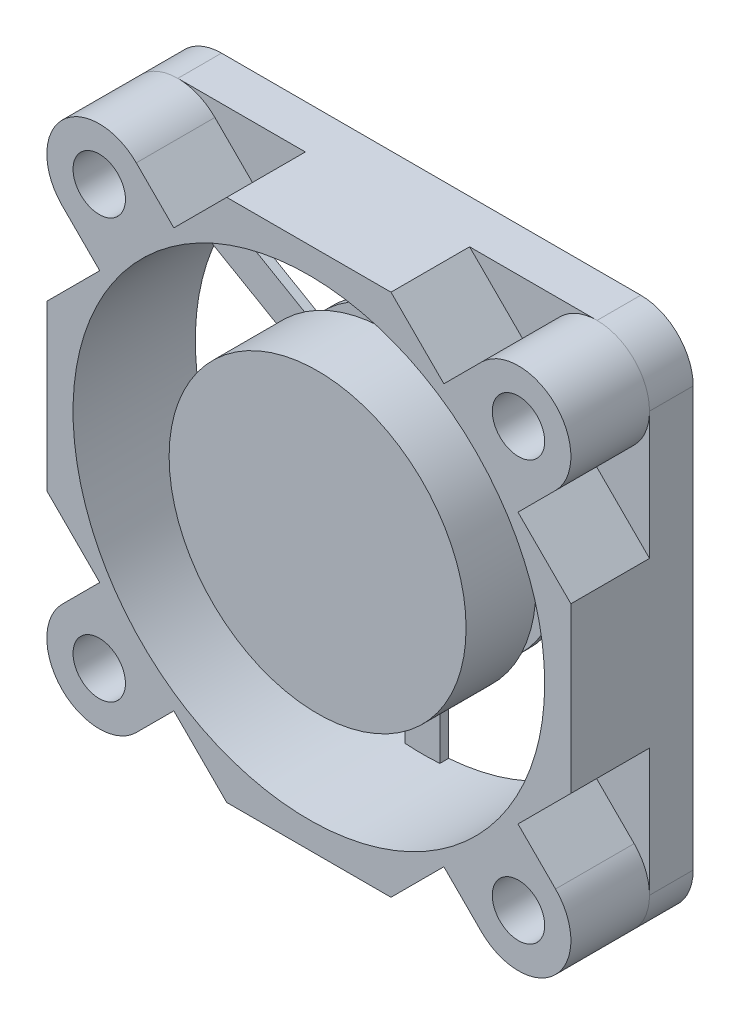
SolidWorks part; units mm, degrees
ref_plane "Спереди" through (0, 0, 0) normal (0, 0, 1) x (1, 0, 0)
ref_plane "Сверху" through (0, 0, 0) normal (0, 1, 0) x (1, 0, 0)
ref_plane "Справа" through (0, 0, 0) normal (1, 0, 0) x (0, 0, -1)
sketch "Эскиз1" plane through (0, 0, 0) normal (0, 0, 1) x (1, 0, 0)
  line L0 (-1, -7.9373) -> (-1, -13.4629)
  line L1 (15, -15) -> (-15, -15)
  line L2 (15, -15) -> (15, 15)
  line L3 (15, 15) -> (-15, 15)
  line L4 (-15, -15) -> (-15, 15)
  line L5 (15, -15) -> (-15, 15) construction
  line L6 (15, 15) -> (-15, -15) construction
  line L7 (0, 0) -> (0, -15) construction
  line L8 (1, -7.9373) -> (1, -13.4629)
  line L9 (-6.3739, 4.8347) -> (-11.1592, 7.5975)
  line L10 (-7.3739, 3.1026) -> (-12.1592, 5.8654)
  line L11 (7.3739, 3.1026) -> (12.1592, 5.8654)
  line L12 (6.3739, 4.8347) -> (11.1592, 7.5975)
  arc A0 (-12.1592, 5.8654) -> (-1, -13.4629) centre (0, 0) ccw
  arc A1 (-7.3739, 3.1026) -> (-1, -7.9373) centre (0, 0) ccw
  arc A2 (1, -7.9373) -> (7.3739, 3.1026) centre (0, 0) ccw
  arc A3 (1, -13.4629) -> (12.1592, 5.8654) centre (0, 0) ccw
  arc A4 (6.3739, 4.8347) -> (-6.3739, 4.8347) centre (0, 0) ccw
  arc A5 (11.1592, 7.5975) -> (-11.1592, 7.5975) centre (0, 0) ccw
  circle A6 centre (-12, 12) radius 1.5
  circle A7 centre (12, 12) radius 1.5
  circle A8 centre (12, -12) radius 1.5
  circle A9 centre (-12, -12) radius 1.5
  point P0 (0, 0)
  point P24 (0, 0)
  dimension "D3" = 27
  dimension "D4" = 16
  dimension "D7" = 3
  dimension "D8" = 12
  dimension "D1" = 30
  dimension "D2" = 30
  dimension "D5" = 1
  dimension "D6" = 3
  dimension "D9" = 2
  dimension "D10" = 2
extrude "Бобышка-Вытянуть1" add sketch "Эскиз1" along normal blind 2.5
sketch "Эскиз2" plane through (0, 0, 2.5) normal (0, 0, 1) x (1, 0, 0)
  line L0 (-9.8787, 14.1213) -> (-7.7291, 11.9718)
  line L1 (0, 15) -> (0, -15) construction
  line L2 (15, 15) -> (-15, 15) construction
  line L3 (-15, -15) -> (15, -15) construction
  line L4 (-7.7291, 15) -> (-7.7291, 11.9718) construction
  line L5 (14.1213, 9.8787) -> (11.9718, 7.7291)
  line L6 (-7.7291, 11.9718) -> (-4.7009, 15)
  line L7 (-15, 15) -> (-9.5459, 9.5459) construction
  line L8 (9.8787, 14.1213) -> (7.7291, 11.9718)
  line L9 (-14.1213, 9.8787) -> (-11.9718, 7.7291)
  line L10 (-11.9718, 7.7291) -> (-15, 4.7009)
  line L11 (9.8787, -14.1213) -> (7.7291, -11.9718)
  line L12 (7.7291, 11.9718) -> (4.7009, 15)
  line L13 (14.1213, -9.8787) -> (11.9718, -7.7291)
  line L14 (-14.1213, -9.8787) -> (-11.9718, -7.7291)
  line L15 (-9.8787, -14.1213) -> (-7.7291, -11.9718)
  line L16 (11.9718, 7.7291) -> (15, 4.7009)
  line L18 (11.9718, -7.7291) -> (15, -4.7009)
  line L22 (7.7291, -11.9718) -> (4.7009, -15)
  line L24 (-7.7291, -11.9718) -> (-4.7009, -15)
  line L28 (-11.9718, -7.7291) -> (-15, -4.7009)
  line L29 (4.7009, 15) -> (-4.7009, 15)
  line L30 (15, 4.7009) -> (15, -4.7009)
  line L31 (4.7009, -15) -> (-4.7009, -15)
  line L32 (-15, -4.7009) -> (-15, 4.7009)
  line L34 (10.7574, 15) -> (7.7291, 11.9718) [skipped]
  line L35 (15, 10.7574) -> (11.9718, 7.7291) [skipped]
  line L36 (-10.7574, -15) -> (-7.7291, -11.9718) [skipped]
  line L37 (-15, -10.7574) -> (-11.9718, -7.7291) [skipped]
  line L38 (15, -10.7574) -> (11.9718, -7.7291) [skipped]
  line L39 (10.7574, -15) -> (7.7291, -11.9718) [skipped]
  circle A0 centre (-12, 12) radius 1.5
  circle A1 centre (-12, 12) radius 1.5 construction
  circle A2 centre (12, 12) radius 1.5
  circle A3 centre (12, -12) radius 1.5
  circle A4 centre (-12, -12) radius 1.5
  circle A5 centre (0, 0) radius 13.5
  arc A6 (11.1592, 7.5975) -> (-11.1592, 7.5975) centre (0, 0) ccw construction
  circle A7 centre (0, 0) radius 14.25 construction
  arc A8 (14.1213, 9.8787) -> (9.8787, 14.1213) centre (12, 12) ccw
  arc A9 (-9.8787, 14.1213) -> (-14.1213, 9.8787) centre (-12, 12) ccw
  arc A10 (9.8787, -14.1213) -> (14.1213, -9.8787) centre (12, -12) ccw
  arc A11 (-14.1213, -9.8787) -> (-9.8787, -14.1213) centre (-12, -12) ccw
  point P58 (0, 0)
  point P77 (0, 0)
  dimension "D1" = 2
  dimension "D3" = 45
  dimension "D5" = 28.5
  dimension "D8" = 4
  dimension "D4" = 3
  dimension "D6" = 90
  dimension "D7" = 4
  dimension "D2" = 2
extrude "Бобышка-Вытянуть2" add sketch "Эскиз2" along normal blind 4.5
fillet "Скругление2" radius 3 4 edges at (-15, -15, 1.25) (15, -15, 1.25) (15, 15, 1.25) (-15, 15, 1.25)
sketch "Эскиз3" plane through (0, 0, 2.5) normal (0, 0, 1) x (1, 0, 0)
  circle A0 centre (0, 0) radius 13.5
  circle A1 centre (0, 0) radius 13.5 construction
extrude "Вырез-Вытянуть1" cut sketch "Эскиз3" against normal blind 2
sketch "Эскиз4" plane through (0, 0, 2.5) normal (0, 0, 1) x (1, 0, 0)
  circle A0 centre (0, 0) radius 8.5
  circle A1 centre (0, 0) radius 7.5
  dimension "D1" = 17
  dimension "D2" = 15
extrude "Бобышка-Вытянуть3" add sketch "Эскиз4" along normal blind 4 separate body
sketch "Эскиз5" plane through (0, 0, 6.5) normal (0, 0, 1) x (1, 0, 0)
  circle A0 centre (0, 0) radius 8.5
  circle A1 centre (0, 0) radius 8.5 construction
extrude "Бобышка-Вытянуть4" add sketch "Эскиз5" against normal blind 2
